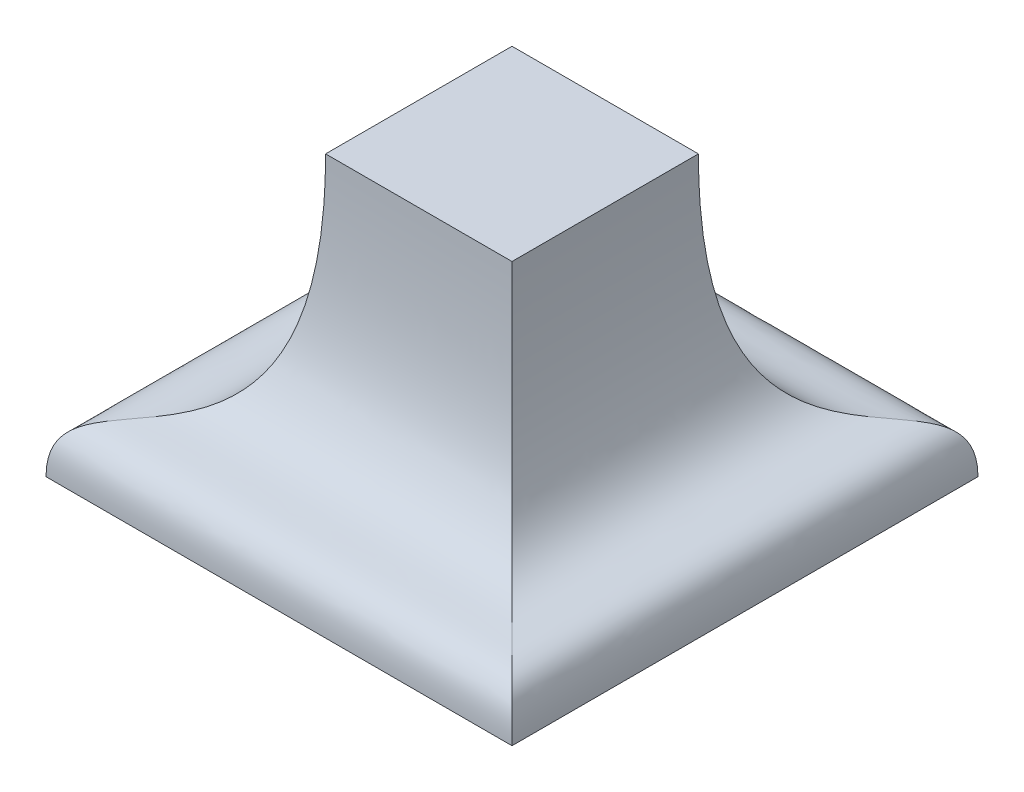
SolidWorks part; units mm, degrees
ref_plane "Front Plane" through (0, 0, 0) normal (0, 0, 1) x (1, 0, 0)
ref_plane "Top Plane" through (0, 0, 0) normal (0, 1, 0) x (1, 0, 0)
ref_plane "Right Plane" through (0, 0, 0) normal (1, 0, 0) x (0, 0, -1)
sketch "Sketch1" plane through (0, 0, 0) normal (0, 1, 0) x (1, 0, 0)
  line L1 (-63.5, -63.5) -> (63.5, -63.5)
  line L2 (-63.5, -63.5) -> (-63.5, 63.5)
  line L3 (-63.5, 63.5) -> (63.5, 63.5)
  line L4 (63.5, -63.5) -> (63.5, 63.5)
  line L5 (-63.5, -63.5) -> (63.5, 63.5) construction
  line L6 (-63.5, 63.5) -> (63.5, -63.5) construction
  point P0 (0, 0)
  dimension "D1" = 127
sketch "Sketch2" plane through (0, 0, 0) normal (1, 0, 0) x (0, 0, -1)
  line L0 (63.5, 0) -> (78.4316, 22.3433)
  line L1 (63.5, 0) -> (-63.5, 0) construction
ref_plane "Plane1" through (0, 76.2, 0) normal (0, 1, 0) x (1, 0, 0)
sketch "Sketch3" plane through (0, 76.2, 0) normal (0, 1, 0) x (1, 0, 0)
  line L0 (-63.5, -63.5) -> (63.5, 63.5) construction
  line L1 (-25.4, -25.4) -> (25.4, -25.4)
  line L2 (-25.4, -25.4) -> (-25.4, 25.4)
  line L3 (-25.4, 25.4) -> (25.4, 25.4)
  line L4 (25.4, -25.4) -> (25.4, 25.4)
  line L5 (-25.4, -25.4) -> (25.4, 25.4) construction
  line L6 (-25.4, 25.4) -> (25.4, -25.4) construction
  line L7 (-63.5, 63.5) -> (63.5, 63.5) construction
  point P0 (0, 0)
  point P6 (35.4295, 35.4295)
  dimension "D1" = 38.1
loft "Loft1" add profiles "Sketch1", "Sketch3" start constraint normal to profile start tangent length 1.04 end constraint normal to profile end tangent length 3 connector at (-63.5, 0, 63.5) connector at (-25.4, 76.2, 25.4)
